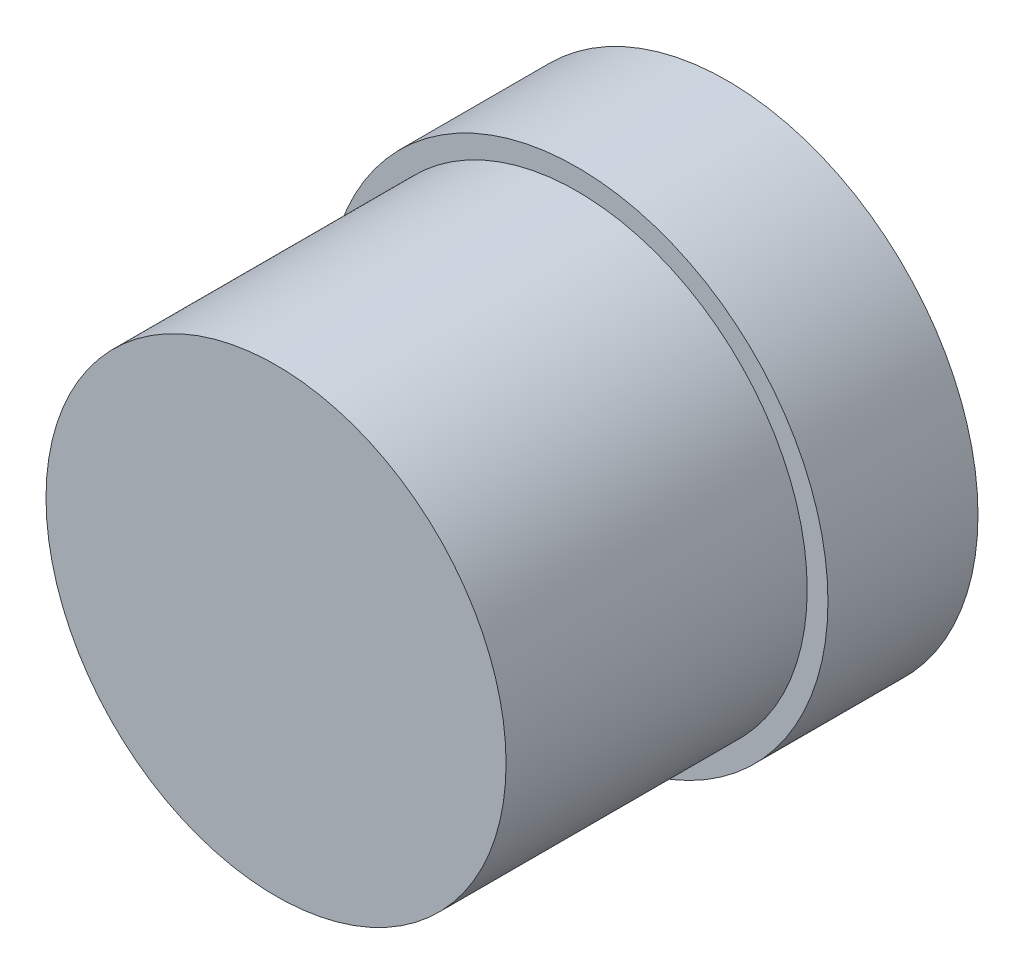
SolidWorks part; units mm, degrees
ref_plane "Front Plane" through (0, 0, 0) normal (0, 0, 1) x (1, 0, 0)
ref_plane "Top Plane" through (0, 0, 0) normal (0, 1, 0) x (1, 0, 0)
ref_plane "Right Plane" through (0, 0, 0) normal (1, 0, 0) x (0, 0, -1)
sketch "Sketch1" plane through (0, 0, 0) normal (0, 0, 1) x (1, 0, 0)
  circle A0 centre (0, 0) radius 38.075
  dimension "D1" = 76.15
extrude "Boss-Extrude1" add sketch "Sketch1" along normal blind 68.5
sketch "Sketch2" plane through (0, 0, 0) normal (0, 0, -1) x (-1, 0, 0)
  circle A0 centre (0, 0) radius 11.5
  dimension "D1" = 23
extrude "Boss-Extrude2" add sketch "Sketch2" along normal blind 6
chamfer "Chamfer1" distance 2 angle 45 1 edges at (-11.5, 0, -6)
sketch "Sketch3" plane through (0, 0, 0) normal (0, 0, -1) x (-1, 0, 0)
  circle A0 centre (0, 0) radius 21.075
  circle A1 centre (0, 0) radius 38.075 construction
  dimension "D1" = 17
extrude "Cut-Extrude1" cut sketch "Sketch3" against normal blind 3
sketch "Sketch8" plane through (0, 0, 68.5) normal (0, 0, 1) x (1, 0, 0)
  circle A0 centre (0, 0) radius 34.925
  circle A1 centre (0, 0) radius 38.075 construction
  circle A2 centre (0, 0) radius 38.075
  dimension "D1" = 69.85
extrude "Cut-Extrude2" cut sketch "Sketch8" against normal blind 45.72
